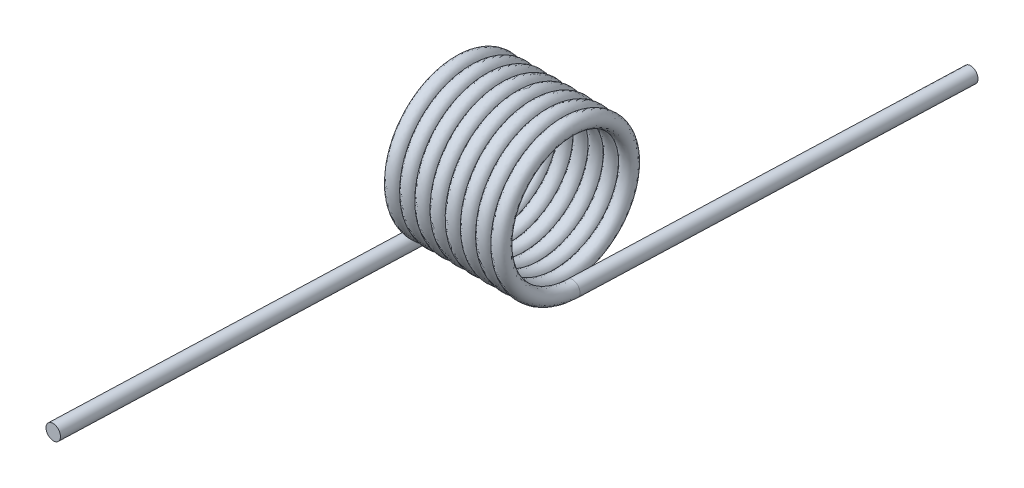
SolidWorks part; units mm, degrees
ref_plane "Front" through (0, 0, 0) normal (0, 0, 1) x (1, 0, 0)
ref_plane "Top" through (0, 0, 0) normal (0, 1, 0) x (1, 0, 0)
ref_plane "Right" through (0, 0, 0) normal (1, 0, 0) x (0, 0, -1)
sketch "Sketch1" plane through (0, 0, 0) normal (1, 0, 0) x (0, 0, -1)
  line L0 (0, 0) -> (0, -7.9375) construction
  line L1 (0, -7.9375) -> (0, -8.9281) construction
  line L2 (0, -8.9281) -> (0, -9.9187) construction
  circle A0 centre (0, 0) radius 7.9375 construction
  circle A1 centre (0, 0) radius 9.9187 construction
  circle A2 centre (0, 0) radius 8.9281
  circle A3 centre (0, -8.9281) radius 0.9906 construction
  circle A4 centre (0, 0) radius 6.35 construction
  dimension "Wire Dia" = 1.9812
  dimension "Spring OD" = 19.8374
  dimension "Max Rod OD" = 12.7
curve "Helix/Spiral1" pitch 2.0066 height 16.0528 radius 8.9281 centre (0, 0, 0) axis (1, 0, 0) start towards (0, 0, -1)
ref_plane "Plane1" through (0, -8.9281, 0) normal (0.0357, 0, -0.9994) x (-0.9994, 0, -0.0357)
sketch "Sketch2" plane through (0, -8.9281, 0) normal (0.0357, 0, -0.9994) x (-0.9994, 0, -0.0357)
  circle A0 centre (0, 0) radius 0.9906
  dimension "D1" = 1.9812
sweep "Sweep1" add profiles "Sketch2" path "Helix/Spiral1"
sketch "Sketch3" plane through (0, 0, 0) normal (-0.0357, 0, 0.9994) x (0.9994, 0, 0.0357)
  circle A1 centre (0, -8.9281) radius 0.9906
  circle A2 centre (0, -8.9281) radius 0.9906
  dimension "D1" = 0
extrude "Extrude1" add sketch "Sketch3" along normal blind 50.8
sketch "Sketch4" plane through (0.0205, 0, -0.5735) normal (0.0357, 0, -0.9994) x (-0.9957, -0.0856, -0.0356)
  circle A1 centre (-15.2194, -10.2686) radius 0.9906
  circle A2 centre (-15.2194, -10.2686) radius 0.9906
  dimension "D1" = 0
extrude "Extrude2" add sketch "Sketch4" along normal blind 50.8
sketch "Sketch5" plane through (0, 0, 0) normal (1, 0, 0) x (0, 0, -1)
  circle A0 centre (0, 0) radius 6.35 construction
  circle A1 centre (0, 0) radius 6.35
ref_plane "Plane2" through (0, 0, 0) normal (1, 0, 0) x (0, 0, -1)
ref_axis "Axis1" through (0, 0, 0) along (1, 0, 0)
equation "\"D4@Helix/Spiral1\"=\"Wire Dia@Sketch1\"+.001"
equation "\"D1@Sketch2\"=\"Wire Dia@Sketch1\""
equation "\"D1@Extrude2\"=\"Leg Length@Extrude1\""
